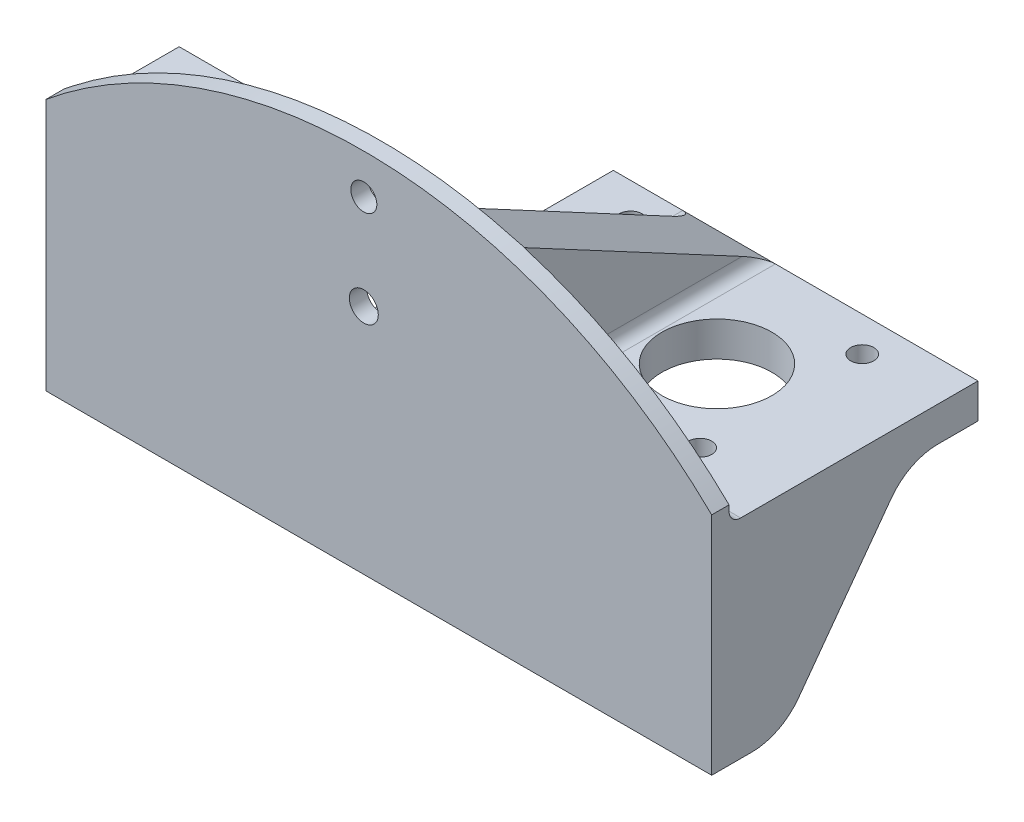
SolidWorks part; units mm, degrees
ref_plane "Front Plane" through (0, 0, 0) normal (0, 0, 1) x (1, 0, 0)
ref_plane "Top Plane" through (0, 0, 0) normal (0, 1, 0) x (1, 0, 0)
ref_plane "Right Plane" through (0, 0, 0) normal (1, 0, 0) x (0, 0, -1)
sketch "Sketch1" plane through (0, 0, 0) normal (0, 1, 0) x (1, 0, 0)
  line L1 (-20, 14) -> (20, 14) construction
  line L2 (-20, 14) -> (-20, -14) construction
  line L3 (-20, -14) -> (20, -14) construction
  line L4 (20, 14) -> (20, -14) construction
  line L5 (-20, 14) -> (20, -14) construction
  line L6 (-20, -14) -> (20, 14) construction
  point P0 (0, 0)
  dimension "D1" = 40
  dimension "D2" = 28
sketch "Sketch2" plane through (0, 0, 0) normal (0, 1, 0) x (1, 0, 0)
  line L1 (-29, 20) -> (29, 20)
  line L2 (-29, 20) -> (-29, -20)
  line L4 (29, 20) -> (29, -20)
  line L5 (-29, 20) -> (29, -20) construction
  line L6 (-29, -20) -> (29, 20) construction
  line L11 (-29, -20) -> (29, -20)
  circle A0 centre (-20, 14) radius 2
  circle A1 centre (20, 14) radius 2
  circle A2 centre (20, -14) radius 2
  circle A3 centre (-20, -14) radius 2
  circle A4 centre (8.9, 0) radius 9.5
  point P0 (0, 0)
  dimension "D3" = 4
  dimension "D4" = 4
  dimension "D5" = 4
  dimension "D6" = 4
  dimension "D7" = 19
  dimension "D8" = 20.1
  dimension "D9" = 0
  dimension "D1" = 58
  dimension "D2" = 40
extrude "Boss-Extrude1" add sketch "Sketch2" along normal blind 6
sketch "Sketch3" plane through (0, 0, 0) normal (0, 1, 0) x (1, 0, 0)
  line L1 (-29, -20) -> (29, -20)
  line L2 (-29, -20) -> (-29, -23)
  line L3 (-29, -23) -> (29, -23)
  line L4 (29, -20) -> (29, -23)
  dimension "D1" = 3
  dimension "D2" = 58
extrude "Boss-Extrude2" add sketch "Sketch3" along normal blind 6 and the other way blind 30
sketch "Sketch7" plane through (0, 0, 0) normal (0, 1, 0) x (1, 0, 0)
  line L1 (-81, -23) -> (34, -23)
  line L2 (-81, -23) -> (-81, -26)
  line L3 (-81, -26) -> (34, -26)
  line L4 (34, -23) -> (34, -26)
  point P4 (0, 0)
  dimension "D1" = 34
  dimension "D2" = 3
  dimension "D3" = 115
  dimension "D4" = 23
extrude "Boss-Extrude4" add sketch "Sketch7" along normal blind 39 and the other way blind 30
sketch "Sketch4" plane through (0, 0, 0) normal (0, 0, 1) x (1, 0, 0)
  line L6 (-81, 39) -> (-81, -30) construction
  line L7 (34, 39) -> (34, -30) construction
  line L8 (-81, 13.6211) -> (-81, 45.2008)
  line L9 (-81, 45.2008) -> (34, 45.2008)
  line L10 (34, 45.2008) -> (34, 8.9632)
  arc A3 (-81, 13.6211) -> (34, 8.9632) centre (-26.1, -52.9) cw
  dimension "D1" = 36.2376
  dimension "D2" = 86.25
  dimension "D3" = 26.1
  dimension "D4" = 52.9
extrude "Cut-Extrude1" cut sketch "Sketch4" along normal through all
sketch "Sketch5" plane through (0, 0, 0) normal (0, 0, 1) x (1, 0, 0)
  line L0 (-26.1, 26.475) -> (-26.1, 10.1) construction
  circle A0 centre (-26.1, 26.475) radius 2.25
  circle A1 centre (-26.1, 10.1) radius 2.5
  dimension "D1" = 4.5
  dimension "D2" = 5
  dimension "D3" = 26.1
  dimension "D4" = 10.1
  dimension "D5" = 26.475
extrude "Cut-Extrude2" cut sketch "Sketch5" along normal through all
ref_plane "Plane1" through (-13, 0, 0) normal (1, 0, 0) x (0, 0, -1)
sketch "Sketch6" plane through (-13, 0, 0) normal (1, 0, 0) x (0, 0, -1)
  line L0 (20, 6) -> (-23, 29)
  line L2 (-23, 29) -> (-23, 6)
  line L3 (-23, 6) -> (20, 6)
  line L4 (-23, 8.9632) -> (-23, 33.35) construction
  dimension "D1" = 23
extrude "Boss-Extrude3" add sketch "Sketch6" along normal blind 10 and the other way blind 2
sketch "Sketch8" plane through (0, 0, 23) normal (0, 0, -1) x (-1, 0, 0)
  line L1 (81, -30) -> (56, -30)
  line L2 (81, -30) -> (81, 10)
  line L3 (81, 10) -> (56, 10)
  line L4 (56, -30) -> (56, 10)
  dimension "D1" = 40
  dimension "D2" = 25
extrude "Boss-Extrude5" add sketch "Sketch8" along normal blind 20
ref_plane "Plane2" through (-33, 0, 0) normal (1, 0, 0) x (0, 0, -1)
sketch "Sketch9" plane through (-33, 0, 0) normal (1, 0, 0) x (0, 0, -1)
  circle A0 centre (0, -11) radius 15.5
  dimension "D1" = 31
  dimension "D2" = 11
extrude "Cut-Extrude3" cut sketch "Sketch9" against normal through all
sketch "Sketch10" plane through (29, 0, 0) normal (1, 0, 0) x (0, 0, -1)
  line L0 (20, 0) -> (20, 6)
  line L1 (20, 6) -> (-26, 6)
  line L2 (-26, -30) -> (-26, 8.9632) construction
  line L3 (-26, 6) -> (-26, -30)
  line L4 (-26, -30) -> (-14, -30)
  line L5 (-3, -30) -> (-23, -30) construction
  line L6 (-14, -30) -> (8, 0)
  line L7 (-20, 0) -> (20, 0) construction
  line L8 (8, 0) -> (20, 0)
  point P4 (0, 0)
  point P16 (0, 0)
  point P17 (0, 0)
  point P18 (0, 0)
  point P19 (-26, -30)
  dimension "D1" = 12
  dimension "D2" = 12
extrude "Boss-Extrude6" add sketch "Sketch10" along normal blind 5
fillet "Fillet2" radius 5 2 edges at (-68.5, 10, 23) (-56, -10, 23)
sketch "Sketch12" plane through (0, 0, 0) normal (0, 0, 1) x (1, 0, 0)
  line L0 (34, -30) -> (34, 8.9632) construction
  line L1 (31, -30) -> (29, -30)
  line L2 (31, -30) -> (31, 0)
  line L3 (31, 0) -> (29, 0)
  line L4 (29, -30) -> (29, 0)
  line L5 (34, 0) -> (29, 0) construction
  point P7 (31, -4.4122)
  dimension "D1" = 2
  dimension "D2" = 3
  dimension "D3" = 0
  dimension "D4" = 30
extrude "Cut-Extrude4" cut sketch "Sketch12" along normal up to surface (20 mm away) and the other way through all up to face at (0, -15, 20)
fillet "Fillet1" radius 2 7 edges at (-15, 6, 1.5) (-3, 6, 1.5) (-3, 17.5, 23) (15.5, 6, 23) (-15, 17.5, 23) (-29, -12, 23) (-9, 29, 23)
fillet "Fillet3" radius 10 2 edges at (32.5, -30, 14) (32.5, 0, -8)
